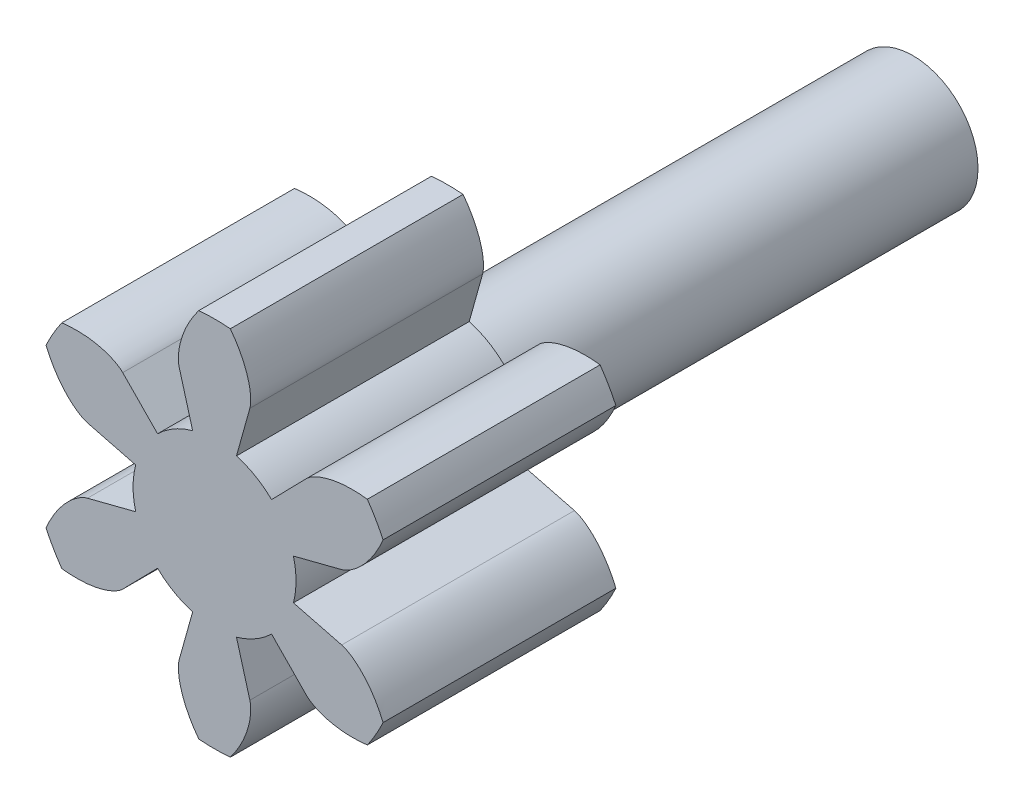
SolidWorks part; units mm, degrees
ref_plane "前视基准面" through (0, 0, 0) normal (0, 0, 1) x (1, 0, 0)
ref_plane "上视基准面" through (0, 0, 0) normal (0, 1, 0) x (1, 0, 0)
ref_plane "右视基准面" through (0, 0, 0) normal (1, 0, 0) x (0, 0, -1)
other "Configuration Table"
sketch "草图1" plane through (0, 0, 0) normal (0, 0, 1) x (1, 0, 0)
  line L0 (0, 0) -> (3, 0) construction
  line L1 (0, 0) -> (2.8978, 0.7765) construction
  line L2 (0, 0) -> (2.7305, 0.701)
  line L3 (2.8978, 0.7765) -> (2.8978, -0.7765) construction
  line L4 (0, 0) -> (2.7305, -0.701)
  circle A0 centre (0, 0) radius 4
  circle A1 centre (0, 0) radius 3 construction
  circle A2 centre (0, 0) radius 1.75
  circle A3 centre (0, 0) radius 2.8191 construction
  circle A4 centre (0, 0) radius 1.4
  spline S0 degree 4 poles (2.7305, 0.701) (2.7514, 0.7063) (2.8083, 0.7255) (2.9105, 0.779) (3.0627, 0.8875) (3.236, 1.0573) (3.4253, 1.3046) (3.6012, 1.6247) (3.742, 2.0003) (3.8364, 2.4221) (3.8779, 2.852) (3.8707, 3.2837) (3.8157, 3.7334) (3.69, 4.2802) (3.4574, 4.9086) (3.0836, 5.5918) (2.5556, 6.2772) (1.9356, 6.8796) (1.2391, 7.3923) (0.4849, 7.8122) (-0.3175, 8.1368) (-1.1468, 8.3674) (-2.0054, 8.5023) (-2.7502, 8.5427) (-3.4127, 8.5171) (-3.8849, 8.4708) (-4.3024, 8.4076) (-4.5772, 8.3558) (-4.9624, 8.2714) (-5.2496, 8.1908) (-5.5362, 8.1071) (-5.6783, 8.056) (-5.7704, 8.0254) knots 0 0 0 0 0 0.005604 0.015718 0.02996 0.048734 0.068727 0.096889 0.125051 0.153212 0.181374 0.209535 0.237696 0.271429 0.327752 0.384075 0.440398 0.496721 0.553044 0.609367 0.66569 0.722013 0.778336 0.834659 0.86282 0.890982 0.909091 0.931818 0.954545 0.977273 1 1 1 1 1 construction
  spline S1 degree 4 poles (2.7305, 0.701) (2.7514, 0.7063) (2.8083, 0.7255) (2.9105, 0.779) (3.0627, 0.8875) (3.236, 1.0573) (3.4253, 1.3046) (3.6012, 1.6247) (3.742, 2.0003) (3.8364, 2.4221) (3.8779, 2.852) (3.8707, 3.2837) (3.8157, 3.7334) (3.69, 4.2802) (3.4574, 4.9086) (3.0836, 5.5918) (2.5556, 6.2772) (1.9356, 6.8796) (1.2391, 7.3923) (0.4849, 7.8122) (-0.3175, 8.1368) (-1.1468, 8.3674) (-2.0054, 8.5023) (-2.7502, 8.5427) (-3.4127, 8.5171) (-3.8849, 8.4708) (-4.2047, 8.4224) (-4.3632, 8.395) (-4.4251, 8.3835) knots 0 0 0 0 0 0.005604 0.015718 0.02996 0.048734 0.068727 0.096889 0.125051 0.153212 0.181374 0.209535 0.237696 0.271429 0.327752 0.384075 0.440398 0.496721 0.553044 0.609367 0.66569 0.722013 0.778336 0.834659 0.86282 0.890982 0.909091 0.909091 0.909091 0.909091 0.909091
  spline S2 degree 4 poles (2.7305, -0.701) (2.7514, -0.7063) (2.8083, -0.7255) (2.9105, -0.779) (3.0627, -0.8875) (3.236, -1.0573) (3.4253, -1.3046) (3.6012, -1.6247) (3.742, -2.0003) (3.8364, -2.4221) (3.8779, -2.852) (3.8707, -3.2837) (3.8157, -3.7334) (3.69, -4.2802) (3.4574, -4.9086) (3.0836, -5.5918) (2.5556, -6.2772) (1.9356, -6.8796) (1.2391, -7.3923) (0.4849, -7.8122) (-0.3175, -8.1368) (-1.1468, -8.3674) (-2.0054, -8.5023) (-2.7502, -8.5427) (-3.4127, -8.5171) (-3.8849, -8.4708) (-4.3024, -8.4076) (-4.5772, -8.3558) (-4.9624, -8.2714) (-5.2496, -8.1908) (-5.5362, -8.1071) (-5.6783, -8.056) (-5.7704, -8.0254) knots 0 0 0 0 0 0.005604 0.015718 0.02996 0.048734 0.068727 0.096889 0.125051 0.153212 0.181374 0.209535 0.237696 0.271429 0.327752 0.384075 0.440398 0.496721 0.553044 0.609367 0.66569 0.722013 0.778336 0.834659 0.86282 0.890982 0.909091 0.931818 0.954545 0.977273 1 1 1 1 1 construction
  spline S3 degree 4 poles (2.7305, -0.701) (2.7514, -0.7063) (2.8083, -0.7255) (2.9105, -0.779) (3.0627, -0.8875) (3.236, -1.0573) (3.4253, -1.3046) (3.6012, -1.6247) (3.742, -2.0003) (3.8364, -2.4221) (3.8779, -2.852) (3.8707, -3.2837) (3.8157, -3.7334) (3.69, -4.2802) (3.4574, -4.9086) (3.0836, -5.5918) (2.5556, -6.2772) (1.9356, -6.8796) (1.2391, -7.3923) (0.4849, -7.8122) (-0.3175, -8.1368) (-1.1468, -8.3674) (-2.0054, -8.5023) (-2.7502, -8.5427) (-3.4127, -8.5171) (-3.8849, -8.4708) (-4.2047, -8.4224) (-4.3632, -8.395) (-4.4251, -8.3835) knots 0 0 0 0 0 0.005604 0.015718 0.02996 0.048734 0.068727 0.096889 0.125051 0.153212 0.181374 0.209535 0.237696 0.271429 0.327752 0.384075 0.440398 0.496721 0.553044 0.609367 0.66569 0.722013 0.778336 0.834659 0.86282 0.890982 0.909091 0.909091 0.909091 0.909091 0.909091
  point P15 (2.8978, 0)
  dimension "齿顶圆直径" = 8
  dimension "分度圆直径" = 6
  dimension "齿根圆直径" = 3.5
  dimension "基圆直径" = 5.6382
  dimension "内孔直径" = 2.8
  dimension "渐近线镜像线夹角" = 15
extrude "凸台-拉伸1" add sketch "草图1" along normal blind 5 contours A0 | A4
extrude "切除-拉伸1" cut sketch "草图1<3>" along normal through all contours A2 S3 A0 S1 region at (3.0753, 0, 0)
sketch "草图1<3>" plane through (0, 0, 0) normal (0, 0, 1) x (1, 0, 0) same geometry as "草图1"
pattern_circular "阵列(圆周)1" count 6 every 60 about axis through (0, 0, 5) along (0, 0, 1) of "切除-拉伸1"
sketch "草图2" plane through (0, 0, 5) normal (0, 0, 1) x (1, 0, 0)
  circle A0 centre (0, 0) radius 1.4
  circle A1 centre (0, 0) radius 1.4 construction
extrude "凸台-拉伸2" add sketch "草图2" against normal blind 15
equation "\"m\"= 1'模数"
equation "\"z\"= 6'齿数"
equation "\"a\"= 20度'压力角"
equation "\"d\"= \"m\" * \"z\"'分度圆直径"
equation "\"da\"= ( \"z\" + 2 ) * \"m\"'齿顶圆直径"
equation "\"df\"= ( \"z\" - 2.5 ) * \"m\"'齿根圆直径"
equation "\"s\"= 0.5 * PI * \"m\"'分度圆齿厚"
equation "\"r\"= 0.38 * \"m\"'齿根圆角"
equation "\"B\"= 0.3 * \"d\"'齿厚"
equation "\"db\"= \"m\" * \"z\" * cos ( \"a\" )'基圆直径"
equation "\"rb\"= \"db\" / 2'基圆半径"
equation "\"齿顶圆直径@草图1\"= \"da\""
equation "\"分度圆直径@草图1\"= \"d\""
equation "\"齿根圆直径@草图1\"= \"df\""
equation "\"基圆直径@草图1\"= \"db\""
equation "\"渐近线镜像线夹角@草图1\"= 360 / 4 / \"z\""
equation "\"h\"= 5'齿轮厚度"
equation "\"ir\"= 2.8'内孔直径"
equation "\"内孔直径@草图1\"= \"ir\""
equation "\"齿轮厚@凸台-拉伸1\"= \"h\""
equation "\"齿轮夹角@阵列(圆周)1\"= 360 / \"z\""
equation "\"齿数@阵列(圆周)1\"= \"z\""
